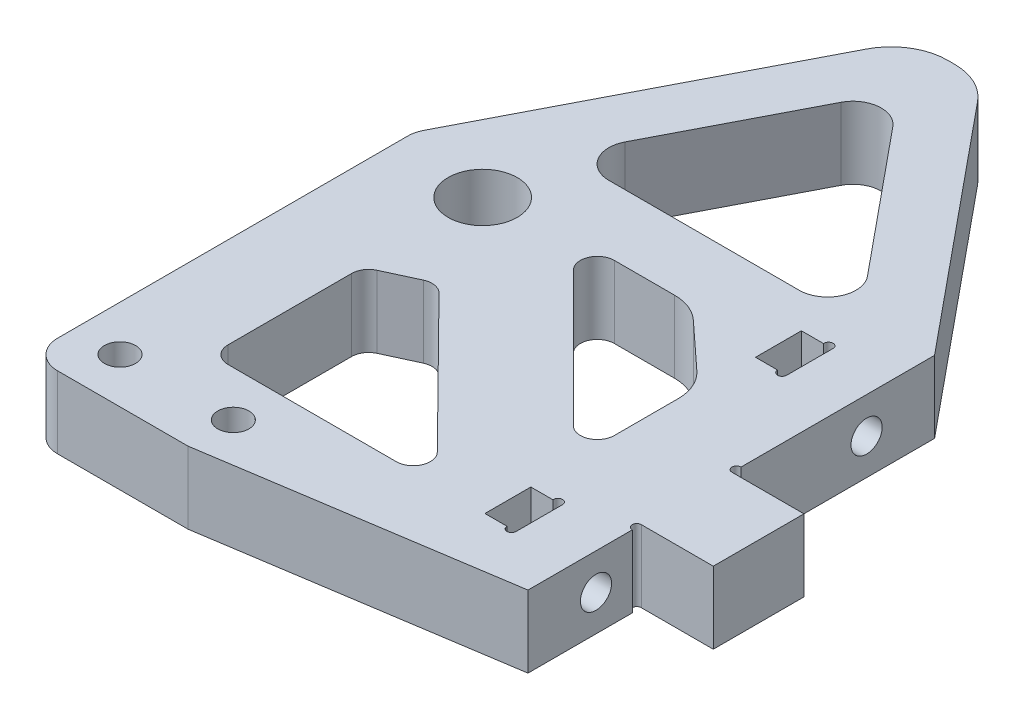
SolidWorks part; units mm, degrees
material "6061 Alloy"
ref_plane "Front Plane" through (0, 0, 0) normal (0, 0, 1) x (1, 0, 0)
ref_plane "Top Plane" through (0, 0, 0) normal (0, 1, 0) x (1, 0, 0)
ref_plane "Right Plane" through (0, 0, 0) normal (1, 0, 0) x (0, 0, -1)
sketch "Sketch1" plane through (0, 0, 0) normal (0, 1, 0) x (1, 0, 0)
  line L1 (-80, 0) -> (-80, 60)
  line L7 (0, 0) -> (-52, -8)
  line L8 (-52, -8) -> (-80, -8)
  line L9 (-80, -8) -> (-80, 0)
  line L10 (-80, 60) -> (-50, 118)
  line L11 (-50, 118) -> (-38, 118)
  line L12 (-38, 118) -> (0, 71.75)
  line L14 (0, 36) -> (12.7, 36)
  line L15 (12.7, 36) -> (12.7, 20)
  line L16 (12.7, 20) -> (0, 20)
  line L18 (0, 18.4) -> (0, 0)
  line L19 (0, 71.75) -> (0, 37.6)
  circle A0 centre (-64, 56) radius 6.1
  circle A3 centre (-72, 0) radius 2.75
  circle A4 centre (-52, 0) radius 2.75
  arc A5 (0, 20) -> (0, 18.4) centre (0, 19.2) ccw
  arc A6 (0, 36) -> (0, 37.6) centre (0, 36.8) cw
  point P23 (12.7, 28)
  dimension "D8" = 12.2
  dimension "D12" = 5.5
  dimension "D16" = 5.5
  dimension "D19" = 0.8
  dimension "D20" = 0.8
  dimension "D1" = 80
  dimension "D2" = 71.75
  dimension "D3" = 60
  dimension "D9" = 16
  dimension "D14" = 8
  dimension "D15" = 20
  dimension "D10" = 8
  dimension "D13" = 8
  dimension "D17" = 56
  dimension "D4" = 58
  dimension "D5" = 30
  dimension "D6" = 12
  dimension "D18" = 12.7
  dimension "D7" = 28
  dimension "D11" = 16
extrude "Boss-Extrude1" add sketch "Sketch1" along normal blind 12.7
fillet "Fillet1" radius 10 2 edges at (-38, 6.35, -118) (-50, 6.35, -118)
sketch "Sketch3" plane through (0, 12.7, 0) normal (0, 1, 0) x (1, 0, 0)
  line L5 (-11.2992, 69.75) -> (-43.4551, 108.8871)
  line L6 (-43.4551, 108.8871) -> (-63.6984, 69.75)
  line L7 (-63.6984, 69.75) -> (-11.2992, 69.75)
  line L10 (0, 71.75) -> (-34.9997, 114.3483) construction
  line L11 (-52.7961, 112.5942) -> (-80, 60) construction
  line L12 (-29.1082, 13.1082) -> (-54.7017, 39.0201)
  line L16 (-80, 60) -> (-80, -8) construction
  line L17 (-63.9447, 34.7442) -> (-63.9447, 8)
  line L18 (-54.7017, 39.0201) -> (-63.9447, 34.7442)
  line L19 (-63.9447, 8) -> (-31.2426, 8)
  line L20 (-42.7574, 58) -> (-32.1279, 58)
  line L21 (-26.7016, 55.8784) -> (-18.5738, 48.3758)
  line L22 (-16, 42.4974) -> (-16, 31.2426)
  line L23 (-21.1213, 29.1213) -> (-44.8787, 52.8787)
  arc A3 (-31.2426, 8) -> (-29.1082, 13.1082) centre (-31.2426, 11) ccw
  arc A4 (-21.1213, 29.1213) -> (-16, 31.2426) centre (-19, 31.2426) ccw
  arc A5 (-44.8787, 52.8787) -> (-42.7574, 58) centre (-42.7574, 55) cw
  arc A6 (-16, 42.4974) -> (-18.5738, 48.3758) centre (-24, 42.4974) ccw
  arc A7 (-26.7016, 55.8784) -> (-32.1279, 58) centre (-32.1279, 50) ccw
  point P19 (-16, 24)
  point P21 (-16, 58)
  point P23 (-50, 58)
  point P24 (-50, 58)
  point P27 (-16, 24)
  point P30 (-24, 8)
  point P31 (-16, 46)
  point P34 (-29, 58)
  point P36 (-58, 42)
  point P38 (-54.7017, 39.0201)
  dimension "D8" = 3
  dimension "D9" = 8
  dimension "D1" = 10
  dimension "D2" = 10
  dimension "D3" = 10
  dimension "D4" = 10
  dimension "D5" = 2
  dimension "D6" = 22
  dimension "D7" = 13
  dimension "D10" = 64
  dimension "D11" = 32
  dimension "D12" = 34
  dimension "D13" = 34
extrude "Cut-Extrude1" cut sketch "Sketch3" against normal through all
fillet "Fillet2" radius 5 3 edges at (-43.4551, 6.35, -108.8871) (-11.2992, 6.35, -69.75) (-63.6984, 6.35, -69.75)
sketch "Sketch4" plane through (0, 12.7, 0) normal (0, 1, 0) x (1, 0, 0)
  line L0 (0, 0) -> (0, 18.4) construction
  line L2 (-15.5, 16) -> (-15.5, 7.9)
  line L4 (-10, 16.1) -> (-10, 7.9)
  line L5 (-15.5, 16) -> (-11.5937, 16)
  line L6 (-15.5, 7.9) -> (-11.6, 7.9)
  line L7 (-15.5, 55.65) -> (-11.6, 55.65)
  line L8 (-10, 63.85) -> (-10, 55.65)
  line L9 (-15.5, 63.75) -> (-11.5937, 63.75)
  line L10 (-15.5, 63.75) -> (-15.5, 55.65)
  arc A0 (-10, 16.1) -> (-11.5937, 16) centre (-10.8, 16.1) ccw
  arc A1 (-10, 7.9) -> (-11.6, 7.9) centre (-10.8, 7.9) cw
  arc A2 (-10, 55.65) -> (-11.6, 55.65) centre (-10.8, 55.65) cw
  arc A3 (-10, 63.85) -> (-11.5937, 63.75) centre (-10.8, 63.85) ccw
  point P4 (-10, 12)
  point P12 (-10, 59.75)
  dimension "D5" = 0.8
  dimension "D1" = 12
  dimension "D2" = 10
  dimension "D3" = 8.2
  dimension "D4" = 5.5
  dimension "D7" = 12
  dimension "D6" = 2
extrude "Cut-Extrude2" cut sketch "Sketch4" against normal through all
sketch "Sketch6" plane through (-10, 0, 0) normal (-1, 0, 0) x (0, 0, 1)
  line L0 (-7.9, 0) -> (-7.9, 12.7) construction
  line L1 (-7.9, 12.7) -> (-16.1, 12.7) construction
  line L2 (-55.65, 0) -> (-55.65, 12.7) construction
  circle A0 centre (-12, 6.35) radius 2.75
  circle A1 centre (-59.75, 6.35) radius 2.75
  dimension "D2" = 5.5
  dimension "D5" = 5.5
  dimension "D1" = 4.1
  dimension "D3" = 6.35
  dimension "D4" = 4.1
extrude "Cut-Extrude3" cut sketch "Sketch6" against normal through all
fillet "Fillet3" radius 3 3 edges at (-54.7017, 6.35, -39.0201) (-63.9447, 6.35, -8) (-63.9447, 6.35, -34.7442)
fillet "Fillet4" radius 5 2 edges at (-80, 6.35, 8) (-80, 6.35, -60)
equation "\"DriveMotorLength\"= 90mm"
equation "\"DriveMotorGap\"= 10mm"
equation "\"AluminumThickness\"= 0.5in"
equation "\"ChassisWidth\"= ( \"DriveMotorLength\" + \"AluminumThickness\" ) * 2 + \"DriveMotorGap\""
equation "\"RepeatMagnumHoleWidth\"= 19.05mm"
equation "\"MortiseWidth\"= 16mm"
equation "\"ChassisScrewThruHole\"= 5.5mm"
equation "\"D12@Sketch1\"=\"ChassisScrewThruHole\""
equation "\"D16@Sketch1\"=\"ChassisScrewThruHole\""
equation "\"MortiseSlotWidth\"= 16.2mm"
equation "\"Dogbone\"= 0.8mm"
equation "\"D19@Sketch1\"=\"Dogbone\""
equation "\"D20@Sketch1\"=\"Dogbone\""
equation "\"D5@Sketch4\"=\"Dogbone\""
equation "\"D2@Sketch6\"=\"ChassisScrewThruHole\""
equation "\"D5@Sketch6\"=\"ChassisScrewThruHole\""
equation "\"D11@Sketch1\"=\"MortiseWidth\""
